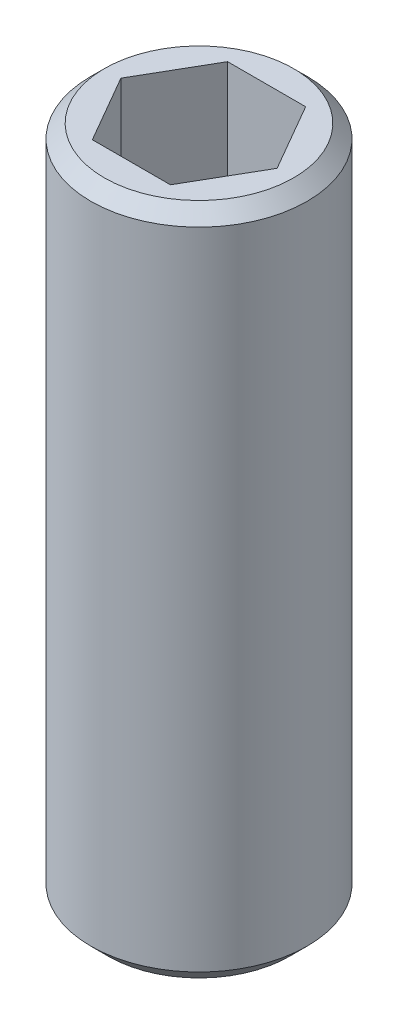
SolidWorks part; units mm, degrees
material "1023 Carbon Steel Sheet (SS)"
ref_plane "Front Plane" through (0, 0, 0) normal (0, 0, 1) x (1, 0, 0)
ref_plane "Top Plane" through (0, 0, 0) normal (0, 1, 0) x (1, 0, 0)
ref_plane "Right Plane" through (0, 0, 0) normal (1, 0, 0) x (0, 0, -1)
sketch "Sketch1" plane through (0, 0, 0) normal (0, 1, 0) x (1, 0, 0)
  circle A0 centre (0, 0) radius 4
  dimension "D1" = 8
extrude "Boss-Extrude1" add sketch "Sketch1" along normal blind 25
hole_wizard "Ø5.0mm Dowel Hole1" positions "Sketch3" profile "Sketch4" hole size "Ø5.0" standard "ISO"
sketch "Sketch3" plane through (0, 25, 0) normal (0, 1, 0) x (1, 0, 0)
  point P0 (0, 0)
sketch "Sketch4" plane through (0, 25, 0) normal (1, 0, 0) x (0, 0, 1)
  line L0 (0, 0) -> (0, 7.5022)
  line L1 (0, 7.5022) -> (2.5, 6)
  line L2 (2.5, 6) -> (2.5, 0)
  line L5 (2.5, 0) -> (0, 0)
  line L10 (0, 7.5022) -> (-2.5, 6) construction
  line L11 (0, -6.35) -> (0, 107.95) construction
  dimension "Hole Dia." = 5
  dimension "Hole Depth" = 6
  dimension "Drill Angle" = 118
sketch "Sketch2" plane through (0, 25, 0) normal (0, 1, 0) x (1, 0, 0)
  line L1 (2.8868, 0) -> (1.4434, 2.5)
  line L2 (1.4434, 2.5) -> (-1.4434, 2.5)
  line L3 (-1.4434, 2.5) -> (-2.8868, 0)
  line L4 (-2.8868, 0) -> (-1.4434, -2.5)
  line L5 (-1.4434, -2.5) -> (1.4434, -2.5)
  line L6 (1.4434, -2.5) -> (2.8868, 0)
  circle A0 centre (0, 0) radius 2.5 construction
  dimension "D1" = 5
extrude "Cut-Extrude1" cut sketch "Sketch2" against normal blind 6 contours L3 L4 L5 L6 L1 L2
chamfer "Chamfer1" distance 0.5 angle 45 1 edges at (0, 25, 4)
chamfer "Chamfer2" distance 0.65 angle 45 1 edges at (0, 0, 4)
